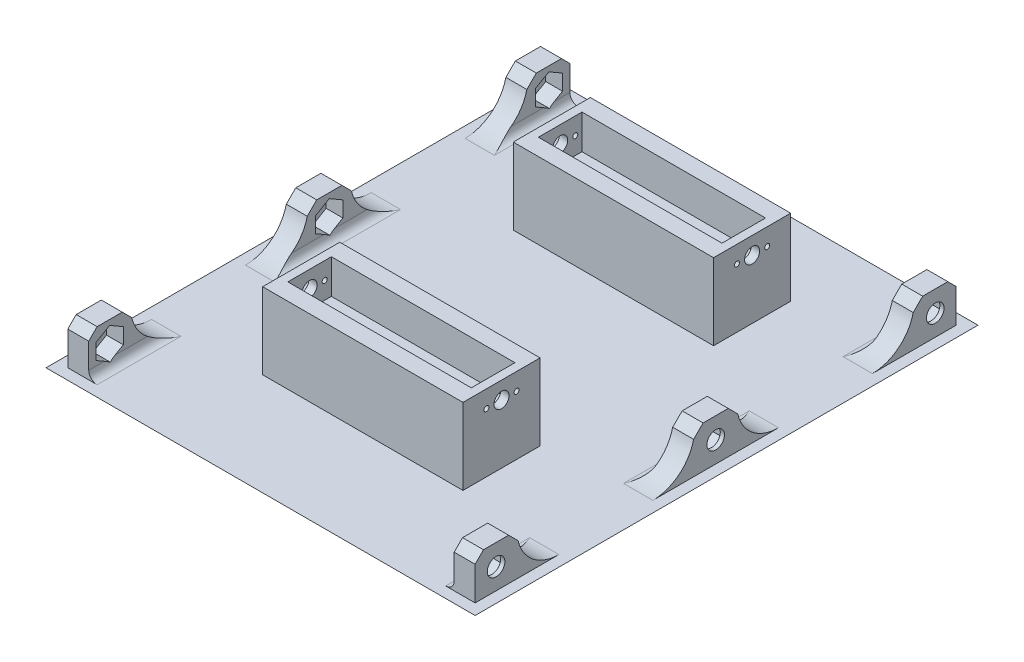
SolidWorks part; units mm, degrees
ref_plane "Front Plane" through (0, 0, 0) normal (0, 0, 1) x (1, 0, 0)
ref_plane "Top Plane" through (0, 0, 0) normal (0, 1, 0) x (1, 0, 0)
ref_plane "Right Plane" through (0, 0, 0) normal (1, 0, 0) x (0, 0, -1)
sketch "Sketch1" plane through (0, 0, 0) normal (0, 1, 0) x (1, 0, 0)
  line L1 (65.024, 76.2) -> (-65.024, 76.2)
  line L2 (65.024, 76.2) -> (65.024, -76.2)
  line L3 (65.024, -76.2) -> (-65.024, -76.2)
  line L4 (-65.024, 76.2) -> (-65.024, -76.2)
  line L5 (65.024, 76.2) -> (-65.024, -76.2) construction
  line L6 (65.024, -76.2) -> (-65.024, 76.2) construction
  point P0 (0, 0)
  dimension "D1" = 130.048
  dimension "D2" = 152.4
extrude "Boss-Extrude1" add sketch "Sketch1" along normal blind 2.54 contours L1 L4 L3 L2
chamfer "Chamfer1" distance 2.54 angle 45 4 edges at (0, 0, -76.2) (-65.024, 0, 0) (0, 0, 76.2) (65.024, 0, 0)
sketch "Sketch2" plane through (0, 2.54, 0) normal (0, 1, 0) x (1, 0, 0)
  line L1 (-27.813, 49.022) -> (27.813, 49.022)
  line L2 (-27.813, 49.022) -> (-27.813, 35.814)
  line L3 (-27.813, 35.814) -> (27.813, 35.814)
  line L4 (27.813, 49.022) -> (27.813, 35.814)
  line L5 (-27.813, 49.022) -> (27.813, 35.814) construction
  line L6 (-27.813, 35.814) -> (27.813, 49.022) construction
  line L7 (-27.813, -26.924) -> (27.813, -26.924)
  line L8 (-27.813, -26.924) -> (-27.813, -40.132)
  line L9 (-27.813, -40.132) -> (27.813, -40.132)
  line L10 (27.813, -26.924) -> (27.813, -40.132)
  line L11 (-27.813, -26.924) -> (27.813, -40.132) construction
  line L12 (-27.813, -40.132) -> (27.813, -26.924) construction
  line L13 (30.353, 54.102) -> (-30.353, 54.102)
  line L14 (30.353, 54.102) -> (30.353, 30.734)
  line L15 (30.353, 30.734) -> (-30.353, 30.734)
  line L16 (-30.353, 54.102) -> (-30.353, 30.734)
  line L17 (30.353, 54.102) -> (-30.353, 30.734) construction
  line L18 (30.353, 30.734) -> (-30.353, 54.102) construction
  line L19 (30.353, -45.212) -> (-30.353, -45.212)
  line L20 (30.353, -45.212) -> (30.353, -21.844)
  line L21 (30.353, -21.844) -> (-30.353, -21.844)
  line L22 (-30.353, -45.212) -> (-30.353, -21.844)
  line L23 (30.353, -45.212) -> (-30.353, -21.844) construction
  line L24 (30.353, -21.844) -> (-30.353, -45.212) construction
  line L26 (-65.024, -72.898) -> (65.024, -72.898) construction
  line L27 (-65.024, 76.2) -> (-65.024, -76.2) construction
  line L28 (65.024, 76.2) -> (65.024, -76.2) construction
  line L29 (65.024, -76.2) -> (-65.024, -76.2) construction
  point P0 (0, 42.418)
  point P5 (0, -33.528)
  point P10 (0, 42.418)
  point P16 (0, -33.528)
  dimension "D1" = 55.626
  dimension "D2" = 13.208
  dimension "D3" = 3.302
  dimension "D4" = 39.37
  dimension "D5" = 2.54
  dimension "D6" = 5.08
  dimension "D7" = 115.316
extrude "Boss-Extrude2" add sketch "Sketch2" along normal blind 23.114
extrude "Boss-Extrude3" add sketch "Sketch2<2>" along normal blind 12.7 contours L10 L7 L8 L9 | L4 L1 L2 L3 region at (0, 2.54, -42.418) region at (0, 2.54, 33.528)
sketch "Sketch2<2>" plane through (0, 2.54, 0) normal (0, 1, 0) x (1, 0, 0) same geometry as "Sketch2"
sketch "Sketch3" plane through (0, 0, 0) normal (1, 0, 0) x (0, 0, -1)
  line L0 (42.418, 25.654) -> (42.418, 15.24) construction
  line L1 (30.734, 25.654) -> (54.102, 25.654) construction
  line L2 (49.022, 15.24) -> (35.814, 15.24) construction
  line L3 (37.846, 20.447) -> (46.99, 20.447) construction
  line L4 (-21.844, 25.654) -> (30.734, 25.654) construction
  line L5 (4.445, 25.654) -> (4.445, 2.54) construction
  line L6 (76.2, 2.54) -> (-76.2, 2.54) construction
  line L7 (-28.956, 20.447) -> (-38.1, 20.447) construction
  line L8 (-33.528, 25.654) -> (-33.528, 15.24) construction
  circle A0 centre (42.418, 20.447) radius 2.286
  circle A1 centre (46.99, 20.447) radius 0.762
  circle A2 centre (37.846, 20.447) radius 0.762
  circle A3 centre (-28.956, 20.447) radius 0.762
  circle A4 centre (-38.1, 20.447) radius 0.762
  circle A5 centre (-33.528, 20.447) radius 2.286
  point P8 (42.418, 20.447)
  dimension "D1" = 1.524
  dimension "D2" = 4.572
  dimension "D3" = 7.62
extrude "Cut-Extrude1" cut sketch "Sketch3" against normal through all both and the other way through all
sketch "Sketch4" plane through (0, 2.54, 0) normal (0, 1, 0) x (1, 0, 0)
  line L0 (0, 76.2) -> (0, -76.2) construction
  line L1 (-61.722, 72.898) -> (-55.372, 72.898)
  line L2 (-61.722, 72.898) -> (-61.722, 60.198)
  line L3 (-61.722, 60.198) -> (-55.372, 60.198)
  line L4 (-55.372, 72.898) -> (-55.372, 60.198)
  line L5 (-61.722, 72.898) -> (-55.372, 60.198) construction
  line L6 (-61.722, 60.198) -> (-55.372, 72.898) construction
  line L7 (-61.722, 6.35) -> (-55.372, 6.35)
  line L8 (-61.722, 6.35) -> (-61.722, -6.35)
  line L9 (-61.722, -6.35) -> (-55.372, -6.35)
  line L10 (-55.372, 6.35) -> (-55.372, -6.35)
  line L11 (-61.722, 6.35) -> (-55.372, -6.35) construction
  line L12 (-61.722, -6.35) -> (-55.372, 6.35) construction
  line L13 (-61.722, -60.198) -> (-55.372, -60.198)
  line L14 (-61.722, -60.198) -> (-61.722, -72.898)
  line L15 (-61.722, -72.898) -> (-55.372, -72.898)
  line L16 (-55.372, -60.198) -> (-55.372, -72.898)
  line L17 (-61.722, -60.198) -> (-55.372, -72.898) construction
  line L18 (-61.722, -72.898) -> (-55.372, -60.198) construction
  line L19 (65.024, 76.2) -> (-65.024, 76.2) construction
  line L20 (65.024, -76.2) -> (-65.024, -76.2) construction
  line L21 (-65.024, 76.2) -> (-65.024, -76.2) construction
  line L22 (61.722, -72.898) -> (55.372, -60.198) construction
  line L23 (61.722, -60.198) -> (55.372, -72.898) construction
  line L24 (61.722, -6.35) -> (55.372, 6.35) construction
  line L25 (61.722, 6.35) -> (55.372, -6.35) construction
  line L26 (61.722, 60.198) -> (55.372, 72.898) construction
  line L27 (61.722, 72.898) -> (55.372, 60.198) construction
  line L28 (55.372, -60.198) -> (55.372, -72.898)
  line L29 (61.722, -72.898) -> (55.372, -72.898)
  line L30 (61.722, -60.198) -> (61.722, -72.898)
  line L31 (61.722, -60.198) -> (55.372, -60.198)
  line L32 (55.372, 6.35) -> (55.372, -6.35)
  line L33 (61.722, -6.35) -> (55.372, -6.35)
  line L34 (61.722, 6.35) -> (61.722, -6.35)
  line L35 (61.722, 6.35) -> (55.372, 6.35)
  line L36 (55.372, 72.898) -> (55.372, 60.198)
  line L37 (61.722, 60.198) -> (55.372, 60.198)
  line L38 (61.722, 72.898) -> (61.722, 60.198)
  line L39 (61.722, 72.898) -> (55.372, 72.898)
  point P4 (-58.547, 66.548)
  point P9 (-58.547, 0)
  point P14 (-58.547, -66.548)
  point P23 (-58.547, 72.898)
  point P38 (58.547, -66.548)
  point P39 (58.547, 0)
  point P40 (58.547, 66.548)
  dimension "D1" = 12.7
  dimension "D2" = 6.35
  dimension "D3" = 3.302
  dimension "D4" = 3.302
  dimension "D5" = 3.302
extrude "Boss-Extrude4" add sketch "Sketch4" along normal blind 12.7
sketch "Sketch5" plane through (0, 0, 0) normal (1, 0, 0) x (0, 0, -1)
  line L0 (0, 15.24) -> (0, 2.54) construction
  line L1 (-6.35, 15.24) -> (6.35, 15.24) construction
  line L2 (76.2, 2.54) -> (-76.2, 2.54) construction
  line L3 (66.548, 15.24) -> (66.548, 2.54) construction
  line L4 (0, 4.124) -> (4.1275, 6.507)
  line L5 (4.1275, 6.507) -> (4.1275, 11.273)
  line L6 (4.1275, 11.273) -> (0, 13.656)
  line L7 (0, 13.656) -> (-4.1275, 11.273)
  line L8 (-4.1275, 11.273) -> (-4.1275, 6.507)
  line L9 (-4.1275, 6.507) -> (0, 4.124)
  line L10 (60.198, 15.24) -> (72.898, 15.24) construction
  line L11 (60.198, 2.54) -> (72.898, 2.54) construction
  line L12 (-66.548, 15.24) -> (-66.548, 2.54) construction
  line L13 (-72.898, 15.24) -> (-60.198, 15.24) construction
  line L14 (-72.898, 2.54) -> (-60.198, 2.54) construction
  line L16 (-66.548, 4.124) -> (-62.4205, 6.507)
  line L17 (-62.4205, 6.507) -> (-62.4205, 11.273)
  line L18 (-62.4205, 11.273) -> (-66.548, 13.656)
  line L19 (-66.548, 13.656) -> (-70.6755, 11.273)
  line L20 (-70.6755, 11.273) -> (-70.6755, 6.507)
  line L21 (-70.6755, 6.507) -> (-66.548, 4.124)
  line L22 (66.548, 4.124) -> (70.6755, 6.507)
  line L23 (70.6755, 6.507) -> (70.6755, 11.273)
  line L24 (70.6755, 11.273) -> (66.548, 13.656)
  line L25 (66.548, 13.656) -> (62.4205, 11.273)
  line L26 (62.4205, 11.273) -> (62.4205, 6.507)
  line L27 (62.4205, 6.507) -> (66.548, 4.124)
  circle A0 centre (0, 8.89) radius 4.1275 construction
  circle A1 centre (0, 8.89) radius 2.667
  circle A2 centre (-66.548, 8.89) radius 4.1275 construction
  circle A3 centre (66.548, 8.89) radius 4.1275 construction
  circle A4 centre (-66.548, 8.89) radius 2.667
  circle A5 centre (66.548, 8.89) radius 2.667
  point P7 (-2.0637, 5.3155)
  dimension "D2" = 5.334
  dimension "D1" = 8.255
extrude "Cut-Extrude2" cut sketch "Sketch5" against normal through all both and the other way through all contours A4 | A1 | A5 region at (0, 8.89, 0) region at (0, 8.89, 66.548) region at (0, 8.89, -66.548)
extrude "Cut-Extrude3" cut sketch "Sketch5<3>" against normal offset from surface 1.27 and the other way offset from surface 1.27 up to face at (-61.722, 8.89, 63.881) other way up to face at (61.722, 8.89, 69.215)
sketch "Sketch5<3>" plane through (0, 0, 0) normal (1, 0, 0) x (0, 0, -1) same geometry as "Sketch5"
fillet "Fillet1" radius 12.7 8 edges at (58.547, 2.54, 60.198) (58.547, 2.54, 6.35) (58.547, 2.54, -6.35) (58.547, 2.54, -60.198) (-58.547, 2.54, 60.198) (-58.547, 2.54, 6.35) (-58.547, 2.54, -6.35) (-58.547, 2.54, -60.198)
fillet "Fillet2" radius 2.54 6 edges at (55.372, 2.54, 60.198) (-55.372, 2.54, 60.198) (-55.372, 2.54, 0) (55.372, 2.54, 0) (55.372, 2.54, -60.198) (-55.372, 2.54, -60.198)
chamfer "Chamfer2" distance 2.54 angle 45 12 edges at (58.547, 15.24, -72.898) (-58.547, 15.24, -72.898) (-58.547, 15.24, 72.898) (58.547, 15.24, 60.198) (58.547, 15.24, 72.898) (58.547, 15.24, 6.35) (58.547, 15.24, -6.35) (58.547, 15.24, -60.198) (-58.547, 15.24, -60.198) (-58.547, 15.24, -6.35) (-58.547, 15.24, 6.35) (-58.547, 15.24, 60.198)
